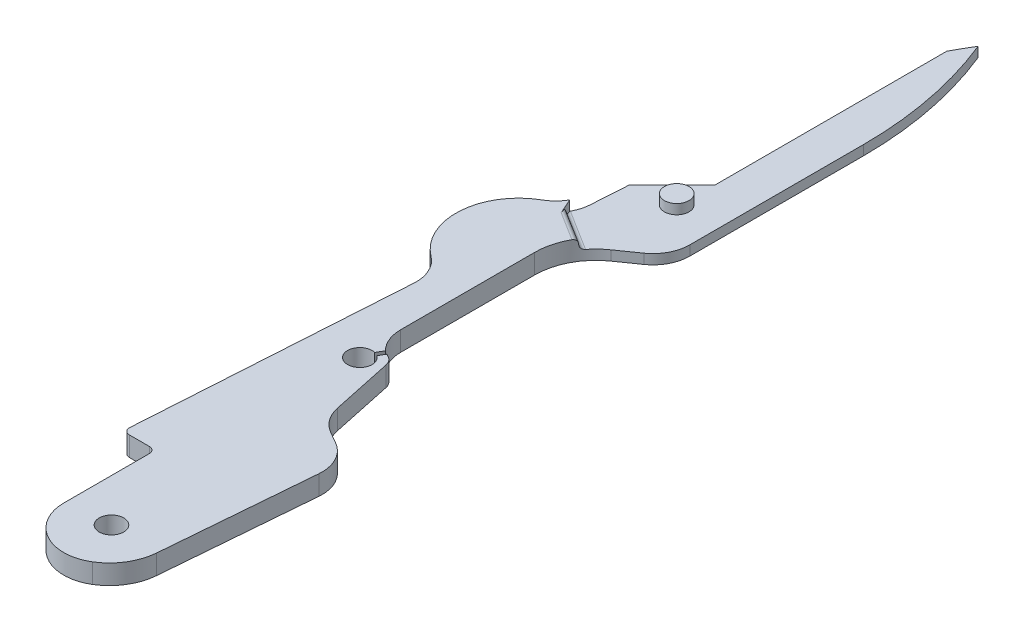
SolidWorks part; units mm, degrees
material "1060 Alloy"
ref_plane "Front Plane" through (0, 0, 0) normal (0, 0, 1) x (1, 0, 0)
ref_plane "Top Plane" through (0, 0, 0) normal (0, 1, 0) x (1, 0, 0)
ref_plane "Right Plane" through (0, 0, 0) normal (1, 0, 0) x (0, 0, -1)
sketch "Sketch1" plane through (0, 0, 0) normal (0, 1, 0) x (1, 0, 0)
  line L0 (0, 63) -> (11.5, 62.2684) construction
  line L1 (0, 0) -> (11.5, 0) construction
  line L2 (0, 0) -> (0, 74) construction
  line L3 (0, 74) -> (11.5, 74) construction
  line L4 (11.5, 0) -> (11.5, 74) construction
  line L5 (0, 47.25) -> (11.5, 46.5184) construction
  line L6 (0, 0) -> (0, 6)
  line L7 (0, 6) -> (1.8653, 35.3216)
  line L8 (9.5, 62.3957) -> (9.5, 46.6457)
  line L9 (9.5, 46.6457) -> (4.5, 43.1446)
  line L10 (4.5, 43.1446) -> (4.5, 27.9946)
  line L11 (4.5, 27.9946) -> (6.3, 26.9554)
  line L12 (6.3, 26.9554) -> (7.7437, 20.1633)
  line L13 (7.7437, 20.1633) -> (11.5, 17.9946)
  line L14 (11.5, 17.9946) -> (10, 0)
  line L15 (10, 0) -> (0, 0)
  line L16 (2.4866, 45.0878) -> (3.6115, 62.7703)
  arc A0 (3.6115, 62.7703) -> (7.2321, 74) centre (27.5631, 61.2466) cw
  arc A1 (7.2321, 74) -> (9.5, 62.3957) centre (-21.3218, 62.3957) cw
  arc A2 (2.4866, 45.0878) -> (1.8653, 35.3216) centre (3.6115, 40.1134) ccw
  dimension "D6" = 6
  dimension "D8" = 24
  dimension "D18" = 5.1
  dimension "D1" = 74
  dimension "D2" = 11.5
  dimension "D3" = 11
  dimension "D4" = 26.75
  dimension "D5" = 93.64
  dimension "D7" = 86.36
  dimension "D9" = 4
  dimension "D10" = 5
  dimension "D11" = 125
  dimension "D12" = 15.15
  dimension "D13" = 10
  dimension "D14" = 132
  dimension "D15" = 120
  dimension "D16" = 1.8
  dimension "D17" = 10
  dimension "D19" = 2
extrude "Boss-Extrude1" add sketch "Sketch1" along normal mid plane 1.6
fillet "Fillet1" radius 4.2 1 edges at (10, 0, 0)
sketch "Sketch2" plane through (0, 0.8, 0) normal (0, 1, 0) x (1, 0, 0)
  line L0 (0, 0) -> (6.1355, 0) construction
  line L1 (0, 6) -> (0, 0) construction
  circle A0 centre (6.5, 4) radius 1
  dimension "D1" = 2
  dimension "D2" = 4
  dimension "D3" = 6.5
extrude "Cut-Extrude1" cut sketch "Sketch2" against normal through all
sketch "Sketch3" plane through (0, 0.8, 0) normal (0, 1, 0) x (1, 0, 0)
  line L0 (5.6401, 27.9693) -> (5.0474, 26.9428)
  line L1 (5.6401, 27.9693) -> (5.9432, 27.7943)
  line L3 (5.9432, 27.7943) -> (5.3675, 26.7972)
  line L4 (6.3, 26.9554) -> (4.5, 27.9946) construction
  arc A0 (5.0474, 26.9428) -> (5.3675, 26.7972) centre (4.8, 25.9739) ccw
  dimension "D2" = 2
  dimension "D5" = 1.5
  dimension "D1" = 0.35
  dimension "D3" = 1
  dimension "D4" = 1.6
extrude "Cut-Extrude2" cut sketch "Sketch3" against normal through all
sketch "Sketch4" plane through (0, 0.8, 0) normal (0, 1, 0) x (1, 0, 0)
  line L0 (6.2991, 72.3751) -> (6.2991, 53.5)
  line L1 (6.2991, 53.5) -> (2.7991, 50)
  line L4 (3.6115, 62.7703) -> (2.4866, 45.0878) construction
  arc A0 (7.2321, 74) -> (3.6115, 62.7703) centre (27.5631, 61.2466) ccw construction
  dimension "D1" = 3.5
  dimension "D2" = 24
  dimension "D3" = 45
extrude "Cut-Extrude-Thin1" cut sketch "Sketch4" against normal through all thin thin type one direction wall 10
sketch "Sketch5" plane through (0, 0.8, 0) normal (0, 1, 0) x (1, 0, 0)
  line L0 (2.4866, 45.0878) -> (13.4551, 38.2222)
  line L1 (13.4551, 38.2222) -> (13.4551, 80.8862)
  line L2 (13.4551, 80.8862) -> (2.4866, 80.8862)
  line L4 (0, 6) -> (0, 0) construction
  line L5 (0, 0) -> (6.1355, 0) construction
  line L6 (2.4866, 80.8862) -> (1.6229, 47.0272)
  line L7 (1.6229, 47.0272) -> (2.4866, 45.0878)
  point P7 (0, 0)
  point P11 (0, 0)
  point P12 (13.4551, 38.2222)
  dimension "D1" = 33.8589
  dimension "D2" = 13.4551
  dimension "D3" = 80.8862
fillet "Fillet2" radius 3 3 edges at (9.5, 0, -46.6457) (2.4866, 0, -45.0878) (1.8653, 0, -35.3216)
extrude "Cut-Extrude4" cut sketch "Sketch5" against normal blind 0.8
fillet "Fillet3" radius 5 1 edges at (4.5, 0, -43.1446)
fillet "Fillet4" radius 0.4 2 edges at (3.91, 0, -44.1968) (3.91, 0.8, -44.1968)
fillet "Fillet5" radius 3 3 edges at (4.5, 0, -27.9946) (11.5, 0, -17.9946) (7.7437, 0, -20.1633)
fillet "Fillet6" radius 1 1 edges at (6.3, 0, -26.9554)
sketch "Sketch6" plane through (0, 0, 0) normal (0, 1, 0) x (1, 0, 0)
  line L0 (0, 0) -> (6.1355, 0) construction
  circle A0 centre (6.14, 50.5) radius 1
  dimension "D3" = 2
  dimension "D1" = 6.14
  dimension "D2" = 50.5
extrude "Boss-Extrude2" add sketch "Sketch6" along normal blind 0.8
sketch "Sketch7" plane through (0, 0.8, 0) normal (0, 1, 0) x (1, 0, 0)
  line L1 (0, 0) -> (3, 0)
  line L2 (0, 0) -> (0, 11.1)
  line L3 (0, 11.1) -> (3, 11.1)
  line L4 (3, 0) -> (3, 11.1)
  dimension "D1" = 11.1
  dimension "D2" = 3
extrude "Cut-Extrude5" cut sketch "Sketch7" against normal through all
fillet "Fillet7" radius 0.5 1 edges at (0.3244, 0, -11.1)
fillet "Fillet8" radius 0.5 1 edges at (3, 0, -11.1)
fillet "Fillet10" radius 3.5 1 edges at (3, 0, 0)
sketch "Sketch8" plane through (0, -0.8, 0) normal (0, -1, 0) x (1, 0, 0)
  line L0 (0, -42.7056) -> (-0.4728, -38.2342)
  arc A0 (0, -42.7056) -> (-0.4728, -38.2342) centre (-1.0813, -40.5592) ccw
extrude "Cut-Extrude6" cut sketch "Sketch8" against normal blind 0.5
fillet "Fillet11" radius 2.4 1 edges at (1.3088, -0.3, -40.3065)
